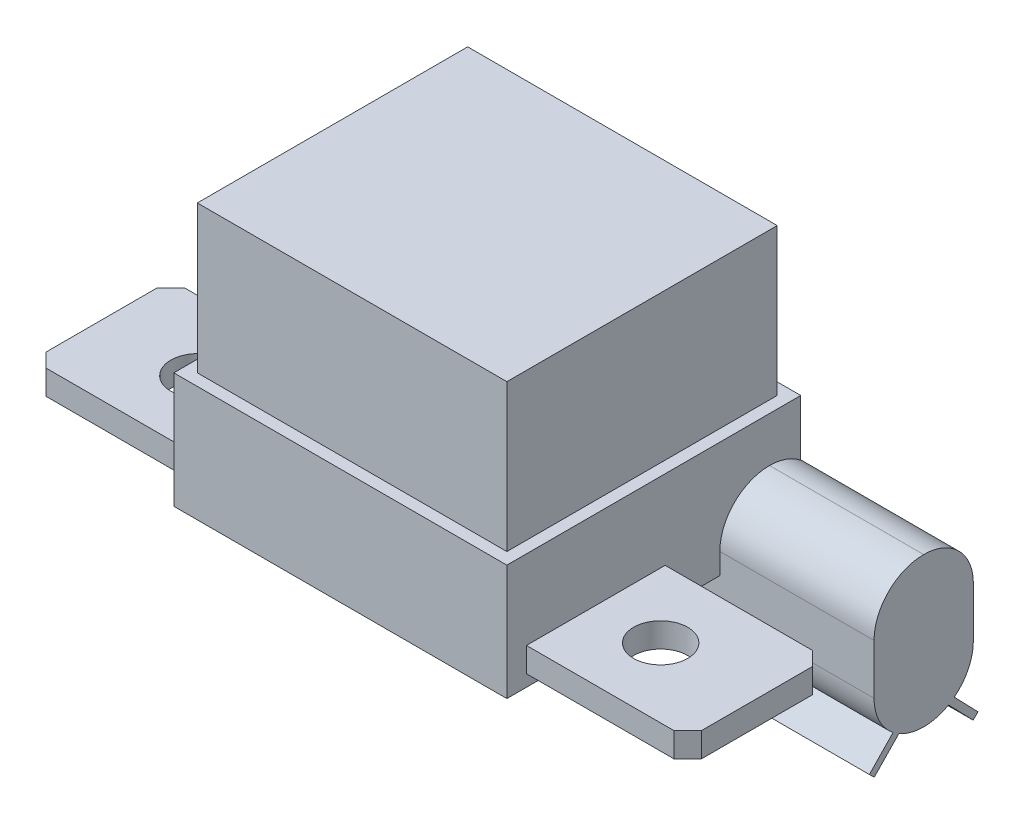
SolidWorks part; units mm, degrees
ref_plane "Front Plane" through (0, 0, 0) normal (0, 0, 1) x (1, 0, 0)
ref_plane "Top Plane" through (0, 0, 0) normal (0, 1, 0) x (1, 0, 0)
ref_plane "Right Plane" through (0, 0, 0) normal (1, 0, 0) x (0, 0, -1)
sketch "Sketch1" plane through (0, 0, 0) normal (0, 1, 0) x (1, 0, 0)
  line L1 (0, 0) -> (43.18, 0)
  line L2 (0, 0) -> (0, 38.1)
  line L3 (0, 38.1) -> (43.18, 38.1)
  line L4 (43.18, 0) -> (43.18, 38.1)
  dimension "D1" = 43.18
  dimension "D2" = 38.1
extrude "Boss-Extrude1" add sketch "Sketch1" along normal blind 14.986
sketch "Sketch3" plane through (0, 14.986, 0) normal (0, 1, 0) x (1, 0, 0)
  line L0 (0, 38.1) -> (0, 0) construction
  line L1 (41.656, 1.524) -> (1.524, 1.524)
  line L2 (41.656, 1.524) -> (41.656, 36.576)
  line L3 (41.656, 36.576) -> (1.524, 36.576)
  line L4 (1.524, 1.524) -> (1.524, 36.576)
  line L5 (41.656, 1.524) -> (1.524, 36.576) construction
  line L6 (41.656, 36.576) -> (1.524, 1.524) construction
  line L7 (43.18, 0) -> (43.18, 38.1) construction
  line L9 (43.18, 38.1) -> (0, 38.1) construction
  point P0 (21.59, 19.05)
  dimension "D1" = 35.052
  dimension "D2" = 40.132
  dimension "D3" = 1.524
  dimension "D4" = 1.524
extrude "Boss-Extrude2" add sketch "Sketch3" along normal blind 19.0754
sketch "Sketch4" plane through (0, 0, 0) normal (-1, 0, 0) x (0, 0, 1)
  line L0 (0, 14.986) -> (0, 0) construction
  line L1 (-2.54, 1.524) -> (-20.5232, 1.524)
  line L2 (-2.54, 1.524) -> (-2.54, 4.699)
  line L3 (-2.54, 4.699) -> (-20.5232, 4.699)
  line L4 (-20.5232, 1.524) -> (-20.5232, 4.699)
  line L5 (-2.54, 1.524) -> (-20.5232, 4.699) construction
  line L6 (-2.54, 4.699) -> (-20.5232, 1.524) construction
  line L7 (-38.1, 0) -> (0, 0) construction
  point P0 (-11.5316, 3.1115)
  dimension "D1" = 2.54
  dimension "D2" = 1.524
  dimension "D3" = 17.9832
  dimension "D4" = 3.175
extrude "Boss-Extrude3" add sketch "Sketch4" along normal blind 20.9042
ref_plane "Plane5" through (21.59, 0, 0) normal (1, 0, 0) x (0, 0, -1)
mirror "Mirror1" about plane through (21.59, 0, 0) normal (1, 0, 0) of "Boss-Extrude3"
sketch "Sketch6" plane through (0, 4.699, 0) normal (0, 1, 0) x (1, 0, 0)
  line L9 (0, 2.54) -> (0, 20.5232) construction
  line L10 (-20.9042, 2.54) -> (0, 2.54) construction
  circle A0 centre (-8.4074, 11.5316) radius 3.5052
  dimension "D1" = 8.4074
  dimension "D2" = 8.9916
extrude "Cut-Extrude2" cut sketch "Sketch6" against normal through all contours A0
mirror "Mirror3" about plane through (21.59, 0, 0) normal (1, 0, 0) of "Cut-Extrude2"
chamfer "Chamfer1" distance 1.7958 angle 45 2 edges at (64.0842, 3.1115, -2.54) (64.0842, 3.1115, -20.5232)
chamfer "Chamfer2" distance 1.7958 angle 45 2 edges at (-20.9042, 3.1115, -2.54) (-20.9042, 3.1115, -20.5232)
sketch "Sketch7" plane through (43.18, 0, 0) normal (1, 0, 0) x (0, 0, -1)
  line L0 (0, 14.986) -> (0, 0) construction
  line L1 (34.036, 9.144) -> (34.0614, 9.144)
  line L2 (27.6098, 2.7178) -> (27.6098, -3.7719)
  line L3 (34.0487, -10.2108) -> (34.0614, -10.2108)
  line L4 (40.4876, 2.7178) -> (40.4876, -3.7846)
  line L5 (34.0487, -10.2108) -> (34.0487, -6.0198)
  line L6 (34.0487, -4.74) -> (27.0073, -12.0316)
  line L7 (34.0487, -6.0198) -> (27.6468, -12.6492)
  line L8 (34.0487, -6.0198) -> (40.4506, -12.6492)
  line L9 (0, 0) -> (38.1, 0) construction
  line L10 (34.0487, -4.74) -> (41.0901, -12.0316)
  line L11 (27.0073, -12.0316) -> (27.6468, -12.6492)
  line L12 (1.524, 34.0614) -> (36.576, 34.0614) construction
  line L13 (40.4506, -12.6492) -> (41.0901, -12.0316)
  arc A0 (27.6098, -3.7719) -> (34.0487, -10.2108) centre (34.0487, -3.7719) ccw
  arc A1 (40.4876, -3.7846) -> (34.0614, -10.2108) centre (34.0614, -3.7846) cw
  arc A2 (34.0614, 9.144) -> (40.4876, 2.7178) centre (34.0614, 2.7178) cw
  arc A3 (34.036, 9.144) -> (27.6098, 2.7178) centre (34.036, 2.7178) ccw
  point P21 (34.036, 2.7178)
  line M9 (0, 0) -> (38.1, 0)
  line M10 (38.1, 0) -> (38.1, 14.986)
  dimension "D5" = 6.4389
  dimension "D6" = 6.4262
  dimension "D7" = 6.4262
  dimension "D8" = 6.4262
  dimension "D1" = 12.8778
  dimension "D2" = 19.3548
  dimension "D3" = 27.6098
  dimension "D4" = 4.191
  dimension "D9" = 44
  dimension "D10" = 44
  dimension "D11" = 12.6492
  dimension "D12" = 12.6492
  dimension "D13" = 44.2722
  dimension "D14" = 0.889
extrude "Boss-Extrude4" add sketch "Sketch7" along normal blind 19.9898 and the other way blind 7.4752 contours L1 A3 L2 A2 M9 M10 | A2 L2 A0 L6 L10 A1 L4 M10 M9 | L7 A0 L5 | A1 L8 L5 L3 | A1 L10 L6 A0 L7 L8 region at (43.18, 4.1568, -33.1597) region at (43.18, -2.6401, -34.7724) region at (43.18, -6.8565, -32.1324) region at (43.18, -8.6172, -32.939) region at (43.18, -8.6187, -35.1597)
extrude "Boss-Extrude5" add sketch "Sketch7<3>" along normal blind 19.9898 contours A0 L6 L11 L7 | L7 L11 L6 L10 L13 L8 region at (43.18, -10.7246, -28.891)
sketch "Sketch7<3>" plane through (43.18, 0, 0) normal (1, 0, 0) x (0, 0, -1) same geometry as "Sketch7"
